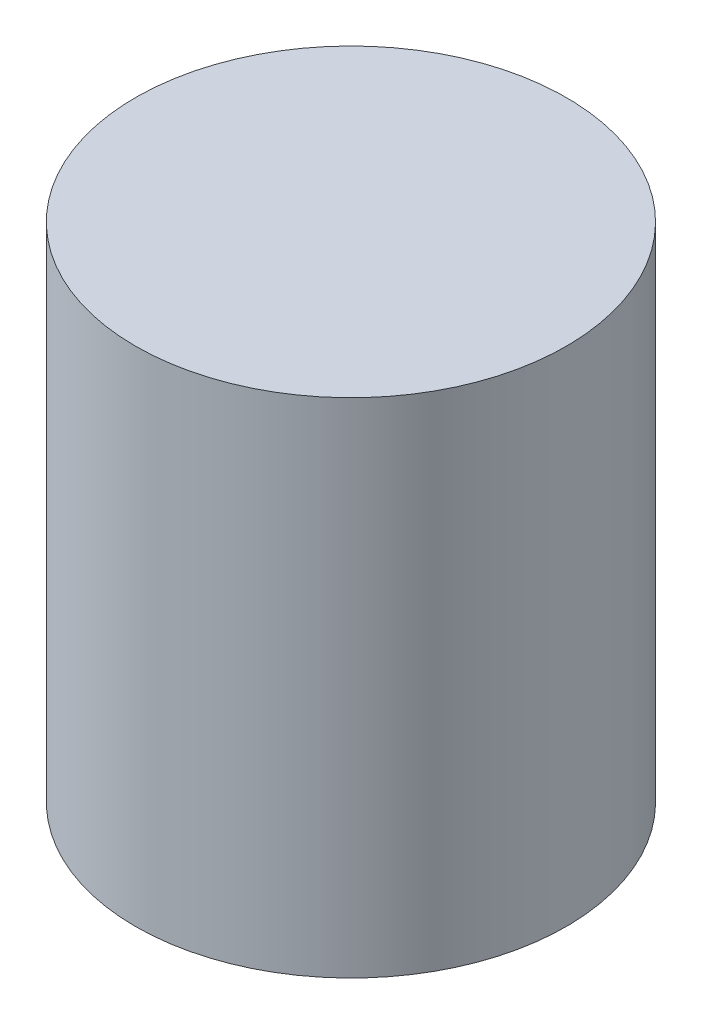
SolidWorks part; units mm, degrees
ref_plane "Front Plane" through (0, 0, 0) normal (0, 0, 1) x (1, 0, 0)
ref_plane "Top Plane" through (0, 0, 0) normal (0, 1, 0) x (1, 0, 0)
ref_plane "Right Plane" through (0, 0, 0) normal (1, 0, 0) x (0, 0, -1)
sketch "Sketch1" plane through (0, 0, 0) normal (0, 1, 0) x (1, 0, 0)
  circle A0 centre (0, 0) radius 1.5
  circle A1 centre (0, 0) radius 0.5
extrude "Boss-Extrude1" add sketch "Sketch1" along normal blind 3
sketch "Sketch2" plane through (0, 3, 0) normal (0, 1, 0) x (1, 0, 0)
  circle A0 centre (0, 0) radius 1.5
extrude "Boss-Extrude2" add sketch "Sketch2" along normal blind 0.5
thread "Thread2" pitch 0.25 method cut profile "Thread Profile2" start angle 0, offset 0, length 3, pitch 0.25, diameter 1
ref_plane "Plane2" through (0.5, 0, 0) normal (0, 0, 1) x (1, 0, 0)
sketch "Thread Profile2" plane through (0.5, 0, 0) normal (0, 0, 1) x (1, 0, 0)
  line L0 (0, 0) -> (0, 0.25) construction
  line L1 (0, 0) -> (0.1353, 0.0781)
  line L2 (0.1353, 0.0781) -> (0.1353, 0.1094)
  line L3 (0.1353, 0.1094) -> (0, 0.1875)
  line L4 (0.1353, 0.0937) -> (0, 0.0937) construction
  line L11 (0, 0) -> (0, 0.1875)
  point P2 (0, 0)
  dimension "Pitch" = 0.25
  dimension "Profile_Angle" = 60
  dimension "Profile_Land" = 0.0312
  dimension "Profile_Height" = 0.1353
